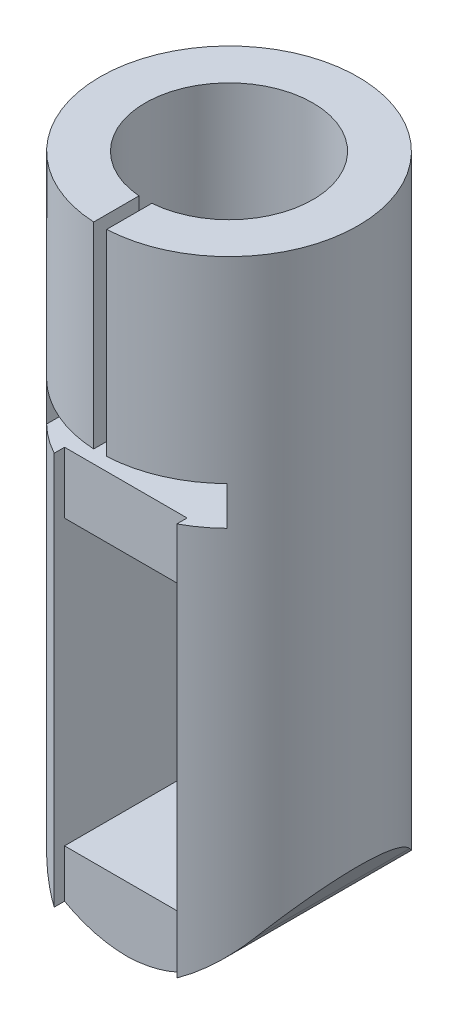
SolidWorks part; units mm, degrees
ref_plane "前视基准面" through (0, 0, 0) normal (0, 0, 1) x (1, 0, 0)
ref_plane "上视基准面" through (0, 0, 0) normal (0, 1, 0) x (1, 0, 0)
ref_plane "右视基准面" through (0, 0, 0) normal (1, 0, 0) x (0, 0, -1)
sketch "草图1" plane through (0, 0, 0) normal (0, 1, 0) x (1, 0, 0)
  circle A0 centre (0, 0) radius 10
  dimension "D1" = 20
extrude "凸台-拉伸1" add sketch "草图1" along normal blind 50
ref_plane "基准面1" through (0, 0, 10) normal (0, 0, 1) x (1, 0, 0)
sketch "草图2" plane through (0, 0, 10) normal (0, 0, 1) x (1, 0, 0)
  line L0 (-10, 0) -> (10, 0) construction
  line L1 (4.75, 0) -> (-4.75, 0)
  line L2 (4.75, 0) -> (4.75, 32)
  line L3 (4.75, 32) -> (-4.75, 32)
  line L4 (-4.75, 0) -> (-4.75, 32)
  line L5 (-4.75, 8.7599) -> (0, 8.7599) construction
  line L6 (0, 8.7599) -> (4.75, 8.7599) construction
  line L7 (0, 0) -> (0, 8.7599) construction
  dimension "D1" = 9.5
  dimension "D2" = 32
extrude "切除-拉伸1" cut sketch "草图2" against normal blind 2
sketch "草图3" plane through (0, 0, 8) normal (0, 0, 1) x (1, 0, 0)
  line L0 (0, 27) -> (0, 32) construction
  line L1 (-4.75, 27) -> (4.75, 27)
  line L2 (-4.75, 27) -> (-4.75, 5)
  line L3 (-4.75, 5) -> (4.75, 5)
  line L4 (4.75, 27) -> (4.75, 5)
  line L5 (-4.75, 32) -> (4.75, 32) construction
  line L6 (0, 5) -> (0, 0) construction
  dimension "D1" = 9.5
  dimension "D2" = 22
extrude "切除-拉伸2" cut sketch "草图3" against normal blind 14
sketch "草图4" plane through (0, 50, 0) normal (0, 1, 0) x (1, 0, 0)
  circle A0 centre (0, 0) radius 6.5
  dimension "D1" = 13
extrude "切除-拉伸3" cut sketch "草图4" against normal blind 18
sketch "草图5" plane through (0, 0, 10) normal (0, 0, 1) x (1, 0, 0)
  line L0 (0, 0) -> (0, 31.76) construction
  line L1 (-7, 31.76) -> (7, 31.76)
  line L2 (-7, 31.76) -> (-7, 34.76)
  line L3 (-7, 34.76) -> (7, 34.76)
  line L4 (7, 31.76) -> (7, 34.76)
  line L5 (-7, 33.26) -> (0, 33.26) construction
  line L6 (0, 33.26) -> (7, 33.26) construction
  dimension "D1" = 3
  dimension "D2" = 14
extrude "切除-拉伸4" cut sketch "草图5" against normal blind 10
sketch "草图6" plane through (0, 0, 10) normal (0, 0, 1) x (1, 0, 0)
  line L0 (-5, 0) -> (-10, 7)
  line L1 (-10, 0) -> (10, 0) construction
  line L2 (-10, 50) -> (-10, 0) construction
  line L3 (-10, 7) -> (-10, 0)
  line L4 (-10, 0) -> (-5, 0)
  line L5 (10, 7) -> (10, 0)
  line L6 (10, 0) -> (10, 50) construction
  line L7 (10, 0) -> (5, 0)
  line L8 (5, 0) -> (10, 7)
  dimension "D1" = 7
  dimension "D2" = 5
extrude "切除-拉伸5" cut sketch "草图6" against normal blind 22
fillet "圆角1" radius 10 1 edges at (-5, 0, 0)
fillet "圆角2" radius 10 1 edges at (5, 0, 0)
sketch "草图7" plane through (0, 0, 10) normal (0, 0, 1) x (1, 0, 0)
  line L0 (0, 0) -> (0, 34.76) construction
  line L1 (-0.5, 50) -> (0.5, 50)
  line L2 (-0.5, 50) -> (-0.5, 34.76)
  line L3 (-0.5, 34.76) -> (0.5, 34.76)
  line L4 (0.5, 50) -> (0.5, 34.76)
  line L5 (10, 50) -> (-10, 50) construction
  line L6 (-6.5, 34.76) -> (6.5, 34.76) construction
  dimension "D1" = 0
  dimension "D2" = 1
  dimension "D3" = 0
extrude "切除-拉伸6" cut sketch "草图7" against normal blind 5
sketch "草图8" plane through (0, 0, 10) normal (0, 0, 1) x (1, 0, 0)
  line L0 (-4.75, 1.2806) -> (-4.75, 31.76) construction
  line L1 (-4.75, 5) -> (4.75, 5)
  line L2 (-4.75, 5) -> (-4.75, 10)
  line L3 (-4.75, 10) -> (4.75, 10)
  line L4 (4.75, 5) -> (4.75, 10)
  line L5 (4.75, 5) -> (4.75, 27) construction
  line L6 (-4.75, 5) -> (4.75, 5) construction
  point P4 (-4.75, 7.5)
  dimension "D1" = 0
  dimension "D2" = 0
  dimension "D3" = 0
  dimension "D4" = 5
extrude "切除-拉伸7" cut sketch "草图8" against normal blind 21
